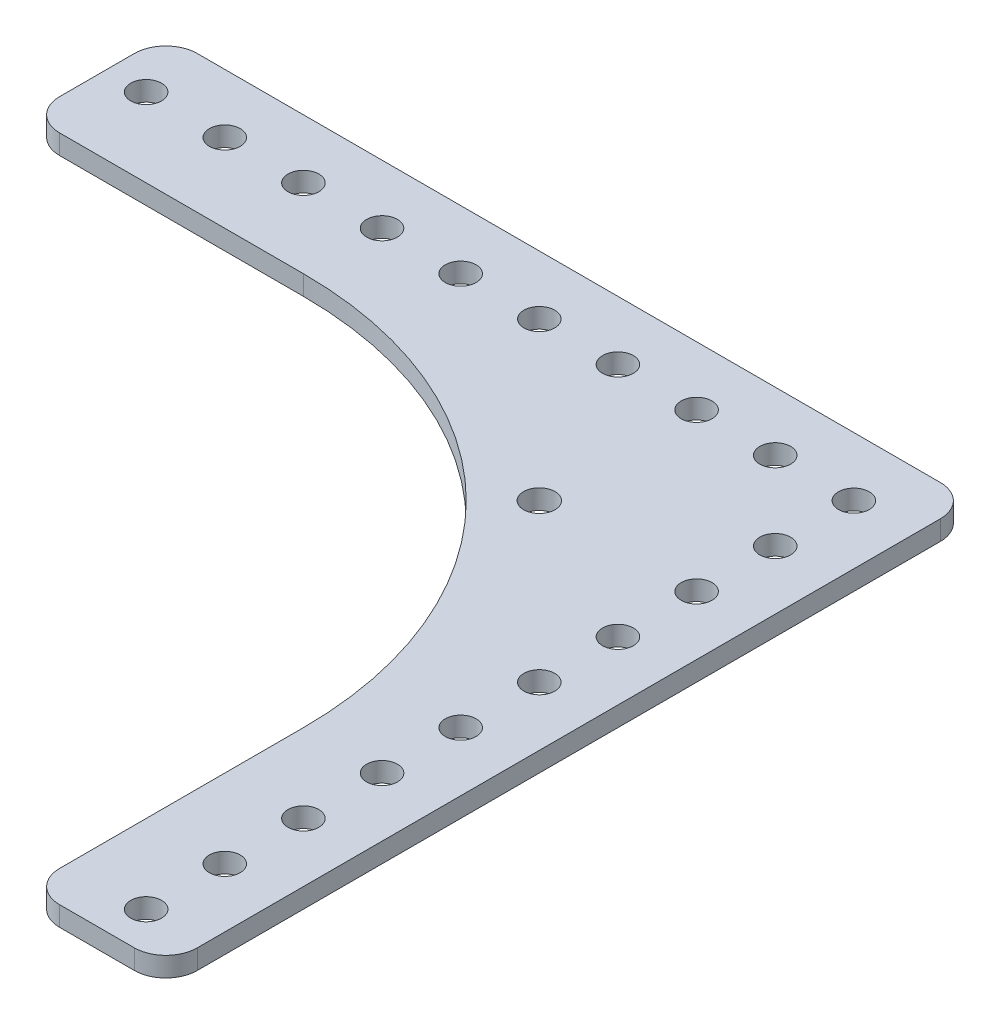
SolidWorks part; units mm, degrees
ref_plane "Front Plane" through (0, 0, 0) normal (0, 0, 1) x (1, 0, 0)
ref_plane "Top Plane" through (0, 0, 0) normal (0, 1, 0) x (1, 0, 0)
ref_plane "Right Plane" through (0, 0, 0) normal (1, 0, 0) x (0, 0, -1)
sketch "Sketch1" plane through (0, 0, 0) normal (0, 1, 0) x (1, 0, 0)
  line B0 (0, 63.5) -> (-33.02, 63.5)
  line B1 (-38.1, 68.58) -> (-38.1, 77.47)
  line B2 (-33.02, 82.55) -> (77.47, 82.55)
  line B3 (82.55, 77.47) -> (82.55, -33.02)
  line B4 (77.47, -38.1) -> (68.58, -38.1)
  line B5 (63.5, -33.02) -> (63.5, 0)
  arc B6 (0, 63.5) -> (63.5, 0) centre (0, 0) cw
  arc B7 (68.58, -38.1) -> (63.5, -33.02) centre (68.58, -33.02) cw
  arc B8 (82.55, -33.02) -> (77.47, -38.1) centre (77.47, -33.02) cw
  arc B9 (77.47, 82.55) -> (82.55, 77.47) centre (77.47, 77.47) cw
  arc B10 (-38.1, 77.47) -> (-33.02, 82.55) centre (-33.02, 77.47) cw
  arc B11 (-33.02, 63.5) -> (-38.1, 68.58) centre (-33.02, 68.58) cw
  circle B12 centre (-28.575, 73.025) radius 2.4892
  circle B13 centre (-15.875, 73.025) radius 2.4892
  circle B14 centre (-3.175, 73.025) radius 2.4892
  circle B15 centre (9.525, 73.025) radius 2.4892
  circle B16 centre (22.225, 73.025) radius 2.4892
  circle B17 centre (34.925, 73.025) radius 2.4892
  circle B18 centre (47.625, 73.025) radius 2.4892
  circle B19 centre (60.325, 73.025) radius 2.4892
  circle B20 centre (73.025, 73.025) radius 2.4892
  circle B21 centre (73.025, 60.325) radius 2.4892
  circle B22 centre (73.025, 47.625) radius 2.4892
  circle B23 centre (73.025, 34.925) radius 2.4892
  circle B24 centre (73.025, 22.225) radius 2.4892
  circle B25 centre (73.025, 9.525) radius 2.4892
  circle B26 centre (73.025, -3.175) radius 2.4892
  circle B27 centre (73.025, -15.875) radius 2.4892
  circle B28 centre (73.025, -28.575) radius 2.4892
  circle B29 centre (50.8, 50.8) radius 2.54
sketch_block_instance "Block-Bumper_Gussest-1"
sketch_block "Block-Bumper_Gussest" parameters "D1"=63.5, "D2"=5.08, "D3"=4.9784, "D8"=5.08, "D4"=9.525, "D5"=9.525, "D6"=12.7, "D7"=9.525, "D9"=31.75, "D10"=31.75
extrude "Boss-Extrude1" add sketch "Sketch1" along normal blind 3.175
sketch "Sketch3" plane through (0, 3.175, 0) normal (0, 1, 0) x (1, 0, 0)
  line L0 (-38.1, 66.675) -> (66.675, 66.675)
  line L1 (66.675, 66.675) -> (66.675, -38.1)
  line L2 (68.58, -38.1) -> (77.47, -38.1) construction
  line L4 (-39.37, 85.725) -> (80.645, 85.725)
  line L5 (85.725, 80.645) -> (85.725, -39.37)
  line L6 (63.5, 0) -> (63.5, -33.02)
  line L7 (68.58, -38.1) -> (77.47, -38.1)
  line L8 (82.55, -33.02) -> (82.55, 77.47)
  line L9 (77.47, 82.55) -> (-33.02, 82.55)
  line L10 (-38.1, 77.47) -> (-38.1, 68.58)
  line L11 (-33.02, 63.5) -> (0, 63.5)
  line L12 (63.5, 0) -> (63.5, -33.02)
  line L17 (-33.02, 63.5) -> (0, 63.5)
  line L19 (-38.1, 77.47) -> (-38.1, 68.58) construction
  line L20 (-33.02, 63.5) -> (-39.37, 63.5)
  line L23 (-44.45, 68.58) -> (-44.45, 80.645)
  line L26 (63.5, -33.02) -> (63.5, -39.37)
  line L27 (68.58, -44.45) -> (80.645, -44.45)
  circle A0 centre (50.8, 50.8) radius 2.54 construction
  circle A1 centre (50.8, 50.8) radius 2.54
  circle A2 centre (-28.575, 73.025) radius 2.4892 construction
  circle A3 centre (-15.875, 73.025) radius 2.4892 construction
  arc A5 (80.645, 85.725) -> (85.725, 80.645) centre (80.645, 80.645) cw
  arc A6 (63.5, 0) -> (0, 63.5) centre (0, 0) ccw
  arc A7 (63.5, -33.02) -> (68.58, -38.1) centre (68.58, -33.02) ccw
  arc A8 (77.47, -38.1) -> (82.55, -33.02) centre (77.47, -33.02) ccw
  arc A9 (82.55, 77.47) -> (77.47, 82.55) centre (77.47, 77.47) ccw
  arc A10 (-33.02, 82.55) -> (-38.1, 77.47) centre (-33.02, 77.47) ccw
  arc A11 (-38.1, 68.58) -> (-33.02, 63.5) centre (-33.02, 68.58) ccw
  arc A12 (63.5, 0) -> (0, 63.5) centre (0, 0) ccw
  circle A19 centre (-3.175, 73.025) radius 2.4892 construction
  circle A20 centre (9.525, 73.025) radius 2.4892 construction
  circle A21 centre (73.025, -28.575) radius 2.4892 construction
  circle A22 centre (73.025, -15.875) radius 2.4892 construction
  circle A23 centre (73.025, -3.175) radius 2.4892 construction
  circle A24 centre (73.025, 9.525) radius 2.4892 construction
  circle A25 centre (73.025, 22.225) radius 2.4892 construction
  circle A26 centre (73.025, 34.925) radius 2.4892 construction
  circle A27 centre (73.025, 47.625) radius 2.4892 construction
  circle A28 centre (73.025, 60.325) radius 2.4892 construction
  circle A29 centre (73.025, 73.025) radius 2.4892 construction
  circle A30 centre (60.325, 73.025) radius 2.4892 construction
  circle A31 centre (47.625, 73.025) radius 2.4892 construction
  circle A32 centre (34.925, 73.025) radius 2.4892 construction
  circle A33 centre (22.225, 73.025) radius 2.4892 construction
  circle A34 centre (73.025, -28.575) radius 2.4892
  circle A35 centre (73.025, -15.875) radius 2.4892
  circle A36 centre (73.025, -3.175) radius 2.4892
  circle A37 centre (73.025, 9.525) radius 2.4892
  circle A38 centre (73.025, 22.225) radius 2.4892
  circle A39 centre (73.025, 34.925) radius 2.4892
  circle A40 centre (73.025, 47.625) radius 2.4892
  circle A41 centre (73.025, 60.325) radius 2.4892
  circle A42 centre (73.025, 73.025) radius 2.4892
  circle A43 centre (60.325, 73.025) radius 2.4892
  circle A44 centre (47.625, 73.025) radius 2.4892
  circle A45 centre (34.925, 73.025) radius 2.4892
  circle A46 centre (22.225, 73.025) radius 2.4892
  circle A47 centre (9.525, 73.025) radius 2.4892
  circle A48 centre (-3.175, 73.025) radius 2.4892
  circle A49 centre (-15.875, 73.025) radius 2.4892
  circle A50 centre (-28.575, 73.025) radius 2.4892
  arc A55 (63.5, -39.37) -> (68.58, -44.45) centre (68.58, -39.37) ccw
  arc A56 (-39.37, 63.5) -> (-44.45, 68.58) centre (-39.37, 68.58) cw
  arc A57 (-39.37, 85.725) -> (-44.45, 80.645) centre (-39.37, 80.645) ccw
  arc A58 (80.645, -44.45) -> (85.725, -39.37) centre (80.645, -39.37) ccw
  line M20 (68.58, -38.1) -> (77.47, -38.1)
  arc M21 (77.47, -38.1) -> (82.55, -33.02) centre (77.47, -33.02) ccw
  line M22 (82.55, -33.02) -> (82.55, 77.47)
  arc M23 (82.55, 77.47) -> (77.47, 82.55) centre (77.47, 77.47) ccw
  line M24 (77.47, 82.55) -> (-33.02, 82.55)
  arc M25 (-33.02, 82.55) -> (-38.1, 77.47) centre (-33.02, 77.47) ccw
  line M26 (-38.1, 77.47) -> (-38.1, 68.58)
  circle M29 centre (-15.875, 73.025) radius 2.4892
  circle M30 centre (-28.575, 73.025) radius 2.4892
  circle M31 centre (-3.175, 73.025) radius 2.4892
  circle M32 centre (9.525, 73.025) radius 2.4892
  circle M33 centre (22.225, 73.025) radius 2.4892
  circle M34 centre (34.925, 73.025) radius 2.4892
  circle M35 centre (47.625, 73.025) radius 2.4892
  circle M36 centre (60.325, 73.025) radius 2.4892
  circle M37 centre (73.025, 73.025) radius 2.4892
  circle M38 centre (73.025, 60.325) radius 2.4892
  circle M39 centre (73.025, 47.625) radius 2.4892
  circle M40 centre (73.025, 34.925) radius 2.4892
  circle M41 centre (73.025, 22.225) radius 2.4892
  circle M42 centre (73.025, 9.525) radius 2.4892
  circle M43 centre (73.025, -3.175) radius 2.4892
  circle M44 centre (73.025, -15.875) radius 2.4892
  circle M45 centre (73.025, -28.575) radius 2.4892
  dimension "D6" = 5.08
  dimension "D9" = 5.08
  dimension "D10" = 5.08
  dimension "D2" = 3.175
  dimension "D3" = 3.175
  dimension "D4" = 19.05
  dimension "D5" = 6.35
  dimension "D7" = 6.35
  dimension "D8" = 19.05
  dimension "D1" = 0
extrude "Boss-Extrude2" add sketch "Sketch3" against normal up to surface (3.175 mm away) contours L0 L1 M20 M21 M22 M23 M24 M25 M26 M30 M32 M34 M36 M38 M40 M42 M44 M45 M43 M41 M39 M37 M35 M33 M31 M29 | L5 A5 L4 M25 M24 M23 M22 M21 | M44 | M45 | M43 | M41 | M42 | M40 | M39 | M38 | M30 | M31 | M32 | M33 | M34 | M35 | M36 | M37 | M29 region at (-36.3316, 3.175, -67.9356) region at (-35.9627, 3.175, -64.2152) region at (73.025, 3.175, 28.575) region at (73.025, 3.175, 15.875) region at (73.025, 3.175, 3.175) region at (73.025, 3.175, -9.525) region at (73.025, 3.175, -22.225) region at (73.025, 3.175, -34.925) region at (73.025, 3.175, -47.625) region at (73.025, 3.175, -60.325) region at (73.025, 3.175, -73.025) region at (60.325, 3.175, -73.025) region at (47.625, 3.175, -73.025) region at (34.925, 3.175, -73.025) region at (22.225, 3.175, -73.025) region at (9.525, 3.175, -73.025) region at (-3.175, 3.175, -73.025) region at (-15.875, 3.175, -73.025) region at (-28.575, 3.175, -73.025) up to face at (73.025, 0, 31.0642)
sketch "Sketch4" plane through (0, 3.175, 0) normal (0, 1, 0) x (1, 0, 0)
  line L0 (-44.45, 66.675) -> (66.675, 66.675)
  line L2 (66.675, 66.675) -> (66.675, -44.45)
  line L4 (-39.37, 63.5) -> (0, 63.5) construction
  line L5 (63.5, 0) -> (63.5, -39.37) construction
  line L6 (-44.45, 68.58) -> (-44.45, 80.645) construction
  line L7 (68.58, -44.45) -> (80.645, -44.45) construction
  line L8 (85.725, 80.645) -> (85.725, -39.37) construction
  line L9 (76.2, 76.2) -> (63.5, 76.2) construction
  line L10 (76.2, 76.2) -> (76.2, 63.5) construction
  circle A0 centre (76.2, 76.2) radius 2.4892
  circle A1 centre (63.5, 76.2) radius 2.4892
  circle A2 centre (50.8, 76.2) radius 2.4892
  circle A3 centre (38.1, 76.2) radius 2.4892
  circle A4 centre (25.4, 76.2) radius 2.4892
  circle A5 centre (12.7, 76.2) radius 2.4892
  circle A6 centre (0, 76.2) radius 2.4892
  circle A7 centre (-12.7, 76.2) radius 2.4892
  circle A8 centre (-25.4, 76.2) radius 2.4892
  circle A10 centre (76.2, 63.5) radius 2.4892
  circle A11 centre (76.2, 50.8) radius 2.4892
  circle A12 centre (76.2, 38.1) radius 2.4892
  circle A13 centre (76.2, 25.4) radius 2.4892
  circle A14 centre (76.2, 12.7) radius 2.4892
  circle A15 centre (76.2, 0) radius 2.4892
  circle A16 centre (76.2, -12.7) radius 2.4892
  circle A17 centre (76.2, -25.4) radius 2.4892
  circle A18 centre (-38.1, 76.2) radius 2.4892
  circle A19 centre (76.2, -38.1) radius 2.4892
  dimension "D3" = 9.525
  dimension "D5" = 4.9784
  dimension "D1" = 3.175
  dimension "D2" = 3.175
  dimension "D4" = 9.525
  dimension "D7" = 12.7
  dimension "D9" = 12.7
  dimension "D6" = 10
  dimension "D8" = 10
extrude "Cut-Extrude1" cut sketch "Sketch4" against normal through all contours A1 | A0 | A10 | A11 | A12 | A2 | A3 | A4 | A17 | A16 | A15 | A14 | A13 | A5 | A6 | A7 | A18 | A8 | A19 region at (76.2, 3.175, -76.2) region at (63.5, 3.175, -76.2) region at (50.8, 3.175, -76.2) region at (38.1, 3.175, -76.2) region at (25.4, 3.175, -76.2) region at (12.7, 3.175, -76.2) region at (0, 3.175, -76.2) region at (-12.7, 3.175, -76.2) region at (-25.4, 3.175, -76.2) region at (76.2, 3.175, -63.5) region at (76.2, 3.175, -50.8) region at (76.2, 3.175, -38.1) region at (76.2, 3.175, -25.4) region at (76.2, 3.175, -12.7) region at (76.2, 3.175, 0) region at (76.2, 3.175, 12.7) region at (76.2, 3.175, 25.4) region at (-38.1, 3.175, -76.2) region at (76.2, 3.175, 38.1)
